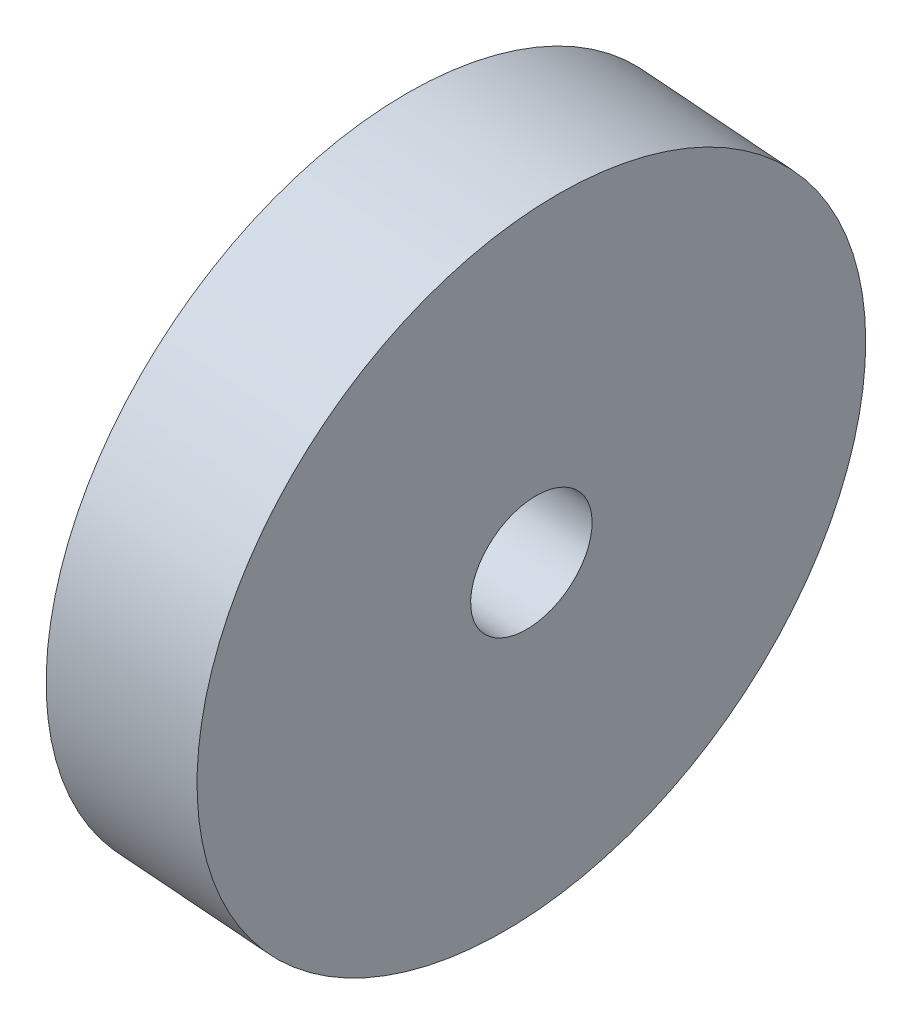
SolidWorks part; units mm, degrees
ref_plane "Front Plane" through (0, 0, 0) normal (0, 0, 1) x (1, 0, 0)
ref_plane "Top Plane" through (0, 0, 0) normal (0, 1, 0) x (1, 0, 0)
ref_plane "Right Plane" through (0, 0, 0) normal (1, 0, 0) x (0, 0, -1)
sketch "Sketch1" plane through (234.2789, -18.689, 0) normal (0.9968, -0.0795, 0) x (0, 0, -1)
  circle A0 centre (-43.1743, 8.5503) radius 13.9827 construction
  circle A1 centre (-43.1743, 8.5503) radius 13.9827
extrude "Boss-Extrude1" add sketch "Sketch1" against normal blind 6.35
sketch "Sketch2" plane through (234.2789, -18.689, 0) normal (0.9968, -0.0795, 0) x (0, 0, -1)
  circle A0 centre (-43.1743, 8.5503) radius 2.54
extrude "Cut-Extrude1" cut sketch "Sketch2" against normal blind 5.08
